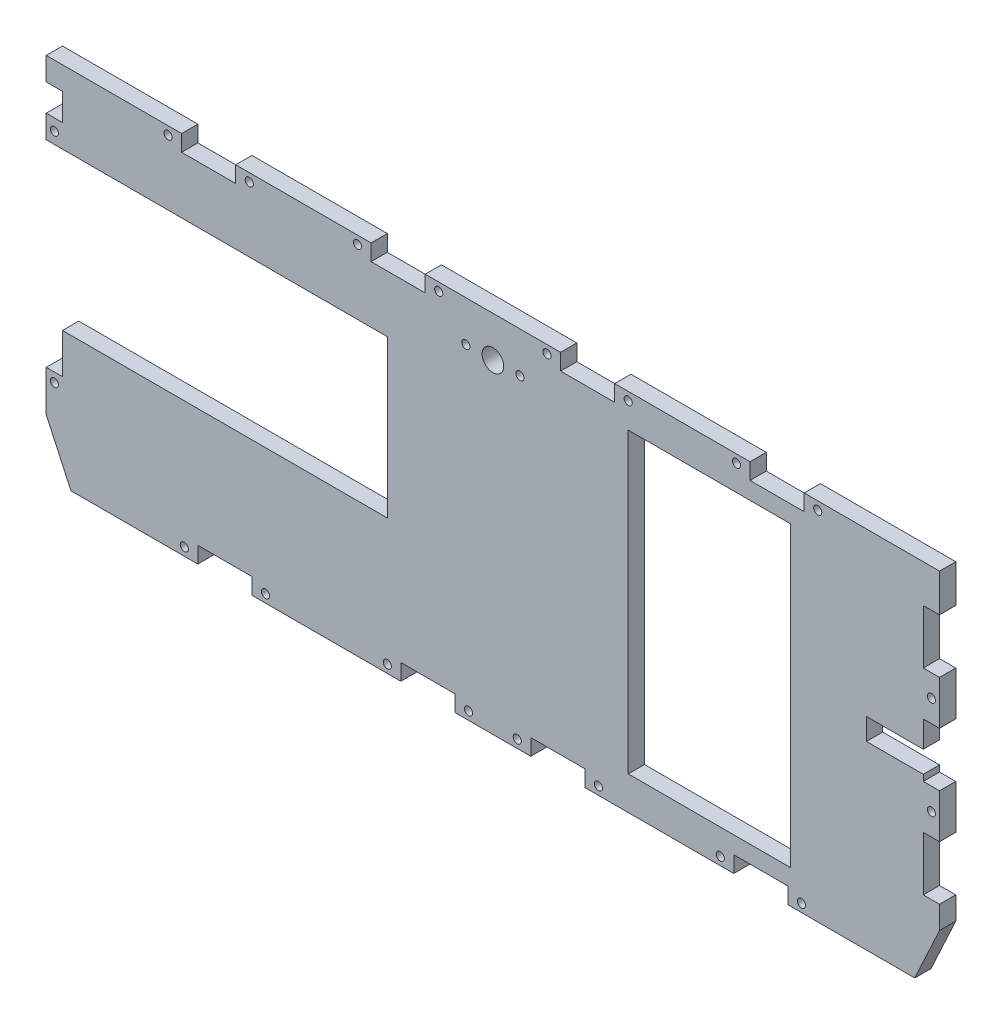
SolidWorks part; units mm, degrees
ref_plane "Plan de face" through (0, 0, 0) normal (0, 0, 1) x (1, 0, 0)
ref_plane "Plan de dessus" through (0, 0, 0) normal (0, 1, 0) x (1, 0, 0)
ref_plane "Plan de droite" through (0, 0, 0) normal (1, 0, 0) x (0, 0, -1)
sketch "Esquisse1" plane through (0, 0, 0) normal (0, 0, 1) x (1, 0, 0)
  line L0 (0, 124.9429) -> (0, -204.46) construction
  line L1 (-165, 96.73) -> (165, 96.73)
  line L2 (165, 96.73) -> (165, -18.27)
  line L3 (165, -18.27) -> (123, -109.0224)
  line L4 (123, -109.0224) -> (-123, -109.0224)
  line L5 (-211.9802, 0) -> (248.5953, 0) construction
  line L6 (-123, -109.0224) -> (-165, -18.27)
  line L7 (-165, -18.27) -> (-165, 96.73)
  dimension "D2" = 165
  dimension "D3" = 330
  dimension "D4" = 100
  dimension "D5" = 115
  dimension "D6" = 100
  dimension "D7" = 246
  dimension "D8" = 205.7524
  dimension "D9" = 96.73
  dimension "D10" = 115
extrude "Boss.-Extru.1" add sketch "Esquisse1" along normal blind 6
sketch "Esquisse3" plane through (0, 0, 0) normal (0, 0, -1) x (-1, 0, 0)
  line L0 (165, 96.73) -> (165, -18.27) construction
  line L1 (165, -3.06) -> (159, -3.06)
  line L2 (165, 69.73) -> (165, -3.06)
  line L3 (39, 11.73) -> (159, 11.73)
  line L4 (159, -3.06) -> (159, 11.73)
  line L5 (123, -109.0224) -> (-123, -109.0224) construction
  line L6 (165, 78.2326) -> (159, 78.2326)
  line L7 (165, 78.2326) -> (165, 88.2326)
  line L8 (165, 88.2326) -> (159, 88.2326)
  line L9 (159, 78.2326) -> (159, 88.2326)
  line L10 (-14, -38.02) -> (-14, -32.02)
  line L11 (109, -38.02) -> (89, -38.02)
  line L12 (109, -38.02) -> (109, -32.02)
  line L13 (109, -32.02) -> (89, -32.02)
  line L15 (0, -209.4812) -> (0, 177.1799) construction
  line L16 (-110, 84.355) -> (-50, 84.355)
  line L17 (-165, 82.73) -> (-159, 82.73)
  line L18 (89, -38.02) -> (89, -32.02)
  line L19 (34, -38.02) -> (14, -38.02)
  line L20 (34, -38.02) -> (34, -32.02)
  line L21 (34, -32.02) -> (14, -32.02)
  line L22 (-165, 82.73) -> (-165, 62.73)
  line L23 (-165, 62.73) -> (-159, 62.73)
  line L24 (-159, 82.73) -> (-159, 62.73)
  line L25 (-165, 46.44) -> (-159, 46.44)
  line L26 (-165, 46.44) -> (-165, 26.44)
  line L27 (-165, 26.44) -> (-159, 26.44)
  line L28 (-159, 46.44) -> (-159, 26.44)
  line L29 (-165, 10.15) -> (-159, 10.15)
  line L30 (-165, 96.73) -> (165, 96.73) construction
  line L31 (115, 96.73) -> (95, 96.73)
  line L32 (115, 96.73) -> (115, 90.73)
  line L33 (115, 90.73) -> (95, 90.73)
  line L34 (95, 96.73) -> (95, 90.73)
  line L35 (-25, 96.73) -> (-25, 90.73)
  line L36 (45, 96.73) -> (25, 96.73)
  line L37 (45, 96.73) -> (45, 90.73)
  line L38 (45, 90.73) -> (25, 90.73)
  line L39 (25, 96.73) -> (25, 90.73)
  line L40 (-45, 90.73) -> (-25, 90.73)
  line L41 (-45, 96.73) -> (-45, 90.73)
  line L42 (-45, 96.73) -> (-25, 96.73)
  line L43 (-95, 96.73) -> (-95, 90.73)
  line L44 (-115, 90.73) -> (-95, 90.73)
  line L45 (-115, 96.73) -> (-115, 90.73)
  line L46 (-115, 96.73) -> (-95, 96.73)
  line L47 (-165, 10.15) -> (-165, -9.85)
  line L48 (14, -38.02) -> (14, -32.02)
  line L49 (-34, -32.02) -> (-14, -32.02)
  line L50 (-34, -38.02) -> (-34, -32.02)
  line L51 (-34, -38.02) -> (-14, -38.02)
  line L52 (-165, -9.85) -> (-159, -9.85)
  line L53 (165, 69.73) -> (39, 69.73)
  line L56 (-159, 10.15) -> (-159, -9.85)
  line L57 (-89, -38.02) -> (-89, -32.02)
  line L58 (-109, -32.02) -> (-89, -32.02)
  line L59 (-109, -38.02) -> (-109, -32.02)
  line L60 (-109, -38.02) -> (-89, -38.02)
  line L62 (-110, 84.355) -> (-110, -25.645)
  line L63 (-110, -25.645) -> (-50, -25.645)
  line L64 (-50, 84.355) -> (-50, -25.645)
  line L65 (-165, -18.27) -> (-165, 96.73) construction
  line L66 (39, 69.73) -> (39, 11.73)
  dimension "D2" = 6
  dimension "D3" = 6
  dimension "D4" = 10
  dimension "D5" = 6
  dimension "D6" = 20
  dimension "D7" = 60
  dimension "D8" = 55
  dimension "D9" = 8.4974
  dimension "D10" = 20
  dimension "D11" = 20
  dimension "D12" = 50
  dimension "D13" = 50
  dimension "D14" = 6
  dimension "D15" = 110
  dimension "D16" = 56
  dimension "D17" = 55
  dimension "D18" = 20
  dimension "D19" = 20
  dimension "D20" = 20
  dimension "D21" = 6
  dimension "D22" = 6
  dimension "D23" = 20
  dimension "D24" = 71.0024
  dimension "D25" = 71.0024
  dimension "D26" = 27
  dimension "D27" = 58
  dimension "D28" = 126
  dimension "D29" = 6.375
  dimension "D30" = 15.21
  dimension "D31" = 6
  dimension "D32" = 6
  dimension "D33" = 6
  dimension "D34" = 14
  dimension "D35" = 16.29
  dimension "D36" = 16.29
extrude "Enlèv. mat.-Extru.2" cut sketch "Esquisse3" against normal blind 6
sketch "Esquisse4" plane through (0, 0, 0) normal (0, 0, -1) x (-1, 0, 0)
  line L0 (159, 78.2326) -> (165, 78.2326) construction
  line L1 (115, 90.73) -> (115, 96.73) construction
  line L2 (120.102, -35.02) -> (4.7601, -35.02) construction
  line L3 (14, -32.02) -> (14, -38.02) construction
  line L4 (34, -38.02) -> (34, -32.02) construction
  line L5 (89, -32.02) -> (89, -38.02) construction
  line L6 (26.5287, 81.73) -> (-31.7243, 81.73) construction
  line L7 (109, -38.02) -> (109, -32.02) construction
  line L8 (165, 78.2326) -> (165, 69.73) construction
  line L9 (-120.102, -35.02) -> (-4.7601, -35.02) construction
  line L10 (-25, 96.73) -> (25, 96.73) construction
  line L11 (143.8632, 93.73) -> (-5, 93.73) construction
  line L12 (45, 96.73) -> (95, 96.73) construction
  line L13 (-162, -27.3544) -> (-162, 100.425) construction
  line L14 (95, 96.73) -> (95, 90.73) construction
  line L15 (45, 90.73) -> (45, 96.73) construction
  line L16 (25, 96.73) -> (25, 90.73) construction
  line L17 (0, 142.2997) -> (0, -202.2086) construction
  line L18 (-165, -18.27) -> (-165, -9.85) construction
  line L19 (-80, 84.355) -> (-80, -25.645) construction
  line L22 (162, -8.8216) -> (162, 103.5789) construction
  line L25 (-50, 84.355) -> (-110, 84.355) construction
  line L26 (-110, -25.645) -> (-50, -25.645) construction
  line L27 (-159, 46.44) -> (-165, 46.44) construction
  line L28 (-165, 26.44) -> (-159, 26.44) construction
  line L31 (159, -3.06) -> (165, -3.06) construction
  circle A1 centre (114, -35.02) radius 1.5
  circle A2 centre (162, 73.9826) radius 1.5
  circle A3 centre (84, -35.02) radius 1.5
  circle A4 centre (39, -35.02) radius 1.5
  circle A5 centre (162, -6.46) radius 1.5
  circle A6 centre (9, -35.02) radius 1.5
  circle A7 centre (-9, -35.02) radius 1.5
  circle A8 centre (-39, -35.02) radius 1.5
  circle A9 centre (-84, -35.02) radius 1.5
  circle A10 centre (120, 93.73) radius 1.5
  circle A11 centre (-114, -35.02) radius 1.5
  circle A12 centre (90, 93.73) radius 1.5
  circle A13 centre (0, 81.73) radius 4
  circle A14 centre (50, 93.73) radius 1.5
  circle A15 centre (20, 93.73) radius 1.5
  circle A16 centre (-162, 18.29) radius 1.5
  circle A17 centre (-162, 54.585) radius 1.5
  circle A18 centre (-20, 93.73) radius 1.5
  circle A19 centre (-50, 93.73) radius 1.5
  circle A20 centre (-90, 93.73) radius 1.5
  circle A21 centre (-120, 93.73) radius 1.5
  circle A22 centre (-10, 81.73) radius 1.5
  circle A23 centre (10, 81.73) radius 1.5
  dimension "D3" = 3
  dimension "D10" = 3
  dimension "D11" = 3
  dimension "D12" = 3
  dimension "D13" = 5
  dimension "D14" = 5
  dimension "D29" = 3
  dimension "D30" = 8.15
  dimension "D31" = 3
  dimension "D32" = 10
  dimension "D33" = 3
  dimension "D34" = 3
  dimension "D35" = 10
  dimension "D40" = 5
  dimension "D8" = 5
  dimension "D15" = 5
  dimension "D16" = 5
  dimension "D20" = 3.4
  dimension "D17" = 3
  dimension "D21" = 3
  dimension "D22" = 3
  dimension "D23" = 3
  dimension "D25" = 8
  dimension "D27" = 8.145
  dimension "D9" = 3
  dimension "D7" = 3
  dimension "D24" = 3
  dimension "D6" = 4.25
  dimension "D26" = 3
  dimension "D28" = 3
  dimension "D36" = 15
  dimension "D38" = 5
  dimension "D42" = 5
extrude "Enlèv. mat.-Extru.3" cut sketch "Esquisse4" against normal blind 6
sketch "Esquisse5" plane through (0, 0, 0) normal (0, 0, -1) x (-1, 0, 0)
  line L0 (45, 96.73) -> (95, 96.73) construction
  line L1 (209.7155, -38.02) -> (-246.3297, -38.02)
  line L2 (209.7155, -38.02) -> (209.7155, -174.249)
  line L3 (209.7155, -174.249) -> (-246.3297, -174.249)
  line L4 (-246.3297, -38.02) -> (-246.3297, -174.249)
  dimension "D1" = 134.75
extrude "Enlèv. mat.-Extru.4" cut sketch "Esquisse5" against normal blind 6
sketch "Esquisse6" plane through (0, 0, 0) normal (0, 0, -1) x (-1, 0, 0)
  line L0 (-159, 26.44) -> (-159, 46.44) construction
  line L1 (-159, 36.73) -> (-138, 36.73)
  line L2 (-159, 36.73) -> (-159, 28.73)
  line L3 (-159, 28.73) -> (-138, 28.73)
  line L4 (-138, 36.73) -> (-138, 28.73)
  line L5 (-165, 96.73) -> (-115, 96.73) construction
  dimension "D1" = 60
  dimension "D2" = 8
  dimension "D3" = 21
extrude "Enlèv. mat.-Extru.5" cut sketch "Esquisse6" against normal blind 10
